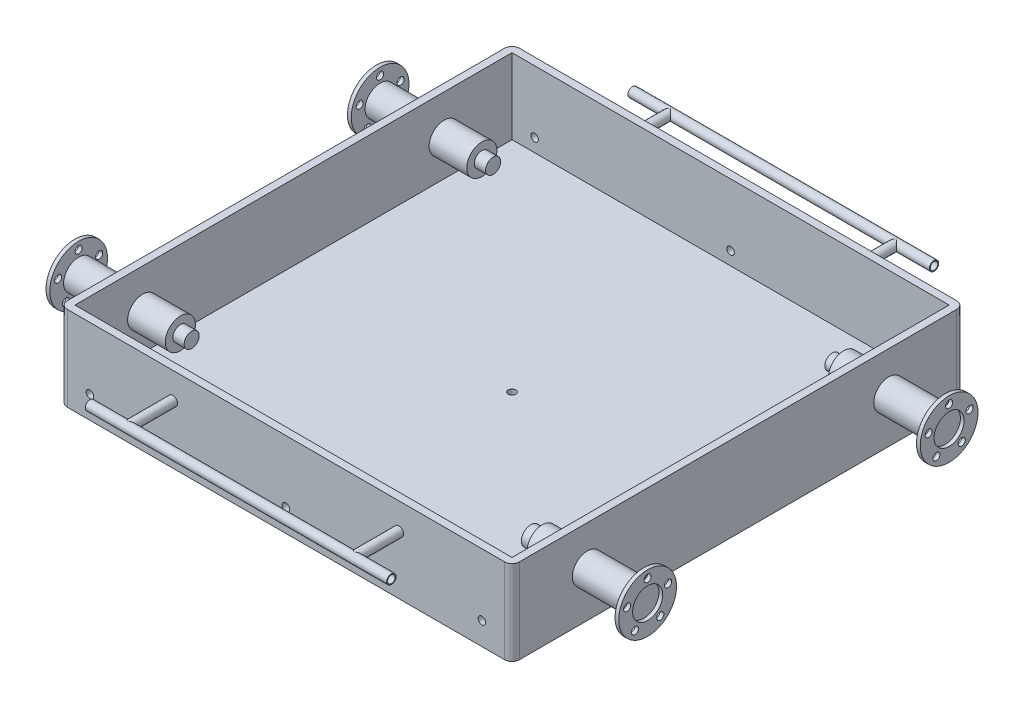
SolidWorks part; units mm, degrees
note: The reader was unsure of these and kept them because the rebuilt part matched: shared geometry of "Sketch13<3>".
ref_plane "Front Plane" through (0, 0, 0) normal (0, 0, 1) x (1, 0, 0)
ref_plane "Top Plane" through (0, 0, 0) normal (0, 1, 0) x (1, 0, 0)
ref_plane "Right Plane" through (0, 0, 0) normal (1, 0, 0) x (0, 0, -1)
sketch "Sketch1" plane through (0, 0, 0) normal (0, 1, 0) x (1, 0, 0)
  line L0 (-580, 580) -> (-580, -580)
  line L1 (-580, 600) -> (580, 600)
  line L2 (-600, 580) -> (-600, -580)
  line L3 (-580, -600) -> (580, -600)
  line L4 (600, 580) -> (600, -580)
  line L5 (-600, 600) -> (600, -600) construction
  line L6 (-600, -600) -> (600, 600) construction
  line L7 (-580, -580) -> (580, -580)
  line L8 (580, 580) -> (580, -580)
  line L9 (-580, 580) -> (580, 580)
  arc A0 (580, -600) -> (600, -580) centre (580, -580) ccw
  arc A1 (-580, 600) -> (-600, 580) centre (-580, 580) ccw
  arc A2 (-600, -580) -> (-580, -600) centre (-580, -580) ccw
  arc A3 (580, 600) -> (600, 580) centre (580, 580) cw
  arc A4 (-580, -580) -> (-580, -580) centre (-580, -580) ccw
  arc A5 (580, -580) -> (580, -580) centre (580, -580) ccw
  arc A6 (580, 580) -> (580, 580) centre (580, 580) cw
  arc A7 (-580, 580) -> (-580, 580) centre (-580, 580) ccw
  point P0 (0, 0)
  dimension "D3" = 20
  dimension "D4" = 20
  dimension "D1" = 1200
  dimension "D2" = 1200
  dimension "D5" = 20
extrude "Boss-Extrude1" add sketch "Sketch1" along normal blind 200
sketch "Sketch2" plane through (-600, 0, 0) normal (-1, 0, 0) x (0, 0, 1)
  line L1 (-600, 0) -> (600, 0)
  line L2 (-600, 0) -> (-600, -25)
  line L3 (-600, -25) -> (600, -25)
  line L4 (600, 0) -> (600, -25)
  dimension "D1" = 25
extrude "Boss-Extrude2" add sketch "Sketch2" against normal up to surface (1200 mm away) up to face at (600, 100, 0)
sketch "Sketch5" plane through (0, 0, 0) normal (0, 1, 0) x (1, 0, 0)
  line L0 (600, -580) -> (600, -600) construction
  line L1 (600, -600) -> (580, -600) construction
  line L2 (600, -580) -> (600, -600)
  line L3 (600, -600) -> (580, -600)
  arc A0 (580, -600) -> (600, -580) centre (580, -580) ccw construction
  arc A1 (580, -600) -> (600, -580) centre (580, -580) ccw
extrude "Cut-Extrude1" cut sketch "Sketch5" against normal blind 300
sketch "Sketch6" plane through (0, 0, 0) normal (0, 1, 0) x (1, 0, 0)
  line L2 (-600, -580) -> (-600, -600)
  line L3 (-600, -600) -> (-580, -600)
  line L4 (-600, -580) -> (-600, -600)
  line L5 (-600, -600) -> (-580, -600)
  arc A1 (-600, -580) -> (-580, -600) centre (-580, -580) ccw
  arc A2 (-600, -580) -> (-580, -600) centre (-580, -580) ccw
  dimension "D1" = 0
extrude "Cut-Extrude2" cut sketch "Sketch6" against normal blind 300
sketch "Sketch7" plane through (0, 0, 0) normal (0, 1, 0) x (1, 0, 0)
  line L2 (600, 580) -> (600, 600)
  line L3 (600, 600) -> (580, 600)
  line L4 (600, 580) -> (600, 600)
  line L5 (600, 600) -> (580, 600)
  arc A1 (600, 580) -> (580, 600) centre (580, 580) ccw
  arc A2 (600, 580) -> (580, 600) centre (580, 580) ccw
  dimension "D1" = 0
extrude "Cut-Extrude3" cut sketch "Sketch7" against normal blind 300
sketch "Sketch8" plane through (0, 0, 0) normal (0, 1, 0) x (1, 0, 0)
  line L2 (-580, 600) -> (-600, 600)
  line L3 (-600, 600) -> (-600, 580)
  line L4 (-580, 600) -> (-600, 600)
  line L5 (-600, 600) -> (-600, 580)
  arc A1 (-580, 600) -> (-600, 580) centre (-580, 580) ccw
  arc A2 (-580, 600) -> (-600, 580) centre (-580, 580) ccw
  dimension "D1" = 0
extrude "Cut-Extrude4" cut sketch "Sketch8" against normal blind 300
sketch "Sketch13" plane through (600, 0, 0) normal (1, 0, 0) x (0, 0, -1)
  line L0 (-600, 200) -> (-600, -25) construction
  line L1 (600, 200) -> (600, -25) construction
  line L2 (-580, -25) -> (580, -25) construction
  circle A0 centre (-400, 95) radius 40
  circle A1 centre (400, 95) radius 40
  circle A2 centre (-400, 95) radius 20
  circle A3 centre (400, 95) radius 20
  dimension "D1" = 80
  dimension "D2" = 80
  dimension "D7" = 40
  dimension "D8" = 40
  dimension "D3" = 200
  dimension "D4" = 200
  dimension "D5" = 120
  dimension "D6" = 120
extrude "Cut-Extrude8" cut sketch "Sketch13" against normal through all contours A2 | A3
extrude "Boss-Extrude7" add sketch "Sketch13<3>" along normal blind 150 and the other way blind 120
sketch "Sketch13<3>" plane through (600, 0, 0) normal (1, 0, 0) x (0, 0, -1) same geometry as "Sketch13"
sketch "Sketch14" plane through (750, 0, 0) normal (1, 0, 0) x (0, 0, -1)
  circle A0 centre (-400, 95) radius 76.655
  circle A1 centre (-400, 95) radius 40
  dimension "D1" = 153.31
extrude "Boss-Extrude8" add sketch "Sketch14" along normal blind 10 separate body
sketch "Sketch15" plane through (760, 0, 0) normal (1, 0, 0) x (0, 0, -1)
  line L0 (-400, 95) -> (-400, 234.5442) construction
  circle A0 centre (-400, 95) radius 57.15 construction
  circle A1 centre (-400, 152.15) radius 9.525
  circle A2 centre (400.6145, 1139.8014) radius 9.525
  circle A3 centre (346.2616, 1122.141) radius 57.15 construction
  circle A4 centre (1587.3303, 683.5728) radius 9.525
  circle A5 centre (1553.7384, 729.8081) radius 57.15 construction
  circle A6 centre (1520.1464, -586.0434) radius 9.525
  circle A7 centre (1553.7384, -539.8081) radius 57.15 construction
  circle A8 centre (291.9088, -914.4807) radius 9.525
  circle A9 centre (346.2616, -932.141) radius 57.15 construction
  circle A10 centre (-345.6471, 112.6603) radius 9.525
  circle A11 centre (-400, 95) radius 57.15 construction
  circle A12 centre (-366.4081, 48.7647) radius 9.525
  circle A13 centre (-400, 95) radius 57.15 construction
  circle A14 centre (-433.5919, 48.7647) radius 9.525
  circle A15 centre (-400, 95) radius 57.15 construction
  circle A16 centre (-454.3529, 112.6603) radius 9.525
  circle A17 centre (-400, 95) radius 57.15 construction
  point P25 (680, 95)
  point P38 (-400, 95)
  dimension "D1" = 114.3
  dimension "D2" = 19.05
  dimension "D3" = 5
  dimension "D4" = 5
extrude "Cut-Extrude9" cut sketch "Sketch15" against normal blind 10
sketch "Sketch18" plane through (750, 0, 0) normal (1, 0, 0) x (0, 0, -1)
  circle A0 centre (400, 95) radius 76.655
  circle A1 centre (400, 95) radius 40 construction
  circle A2 centre (400, 95) radius 40
  dimension "D1" = 153.31
extrude "Boss-Extrude9" add sketch "Sketch18" along normal blind 10 separate body
sketch "Sketch19" plane through (760, 0, 0) normal (1, 0, 0) x (0, 0, -1)
  line L0 (400, 95) -> (400, 254.3445) construction
  circle A0 centre (400, 95) radius 57.155 construction
  circle A1 centre (400, 152.155) radius 9.525
  circle A2 centre (454.3576, 112.6619) radius 9.525
  circle A3 centre (433.5949, 48.7606) radius 9.525
  circle A4 centre (366.4051, 48.7606) radius 9.525
  circle A5 centre (345.6424, 112.6619) radius 9.525
  point P17 (400, 95)
  dimension "D1" = 114.31
  dimension "D2" = 19.05
  dimension "D3" = 5
extrude "Cut-Extrude11" cut sketch "Sketch19" against normal blind 10
sketch "Sketch20" plane through (-600, 0, 0) normal (-1, 0, 0) x (0, 0, 1)
  circle A0 centre (400, 95) radius 20
  circle A1 centre (400, 95) radius 40
  circle A2 centre (-400, 95) radius 20
  circle A3 centre (-400, 95) radius 40
extrude "Boss-Extrude10" add sketch "Sketch20" along normal blind 150 and the other way blind 120
sketch "Sketch21" plane through (-750, 0, 0) normal (-1, 0, 0) x (0, 0, 1)
  circle A0 centre (-400, 95) radius 76.655
  circle A1 centre (400, 95) radius 76.655
  circle A2 centre (-400, 95) radius 57.15 construction
  circle A3 centre (400, 95) radius 57.15 construction
  circle A4 centre (-400, 152.15) radius 9.525
  circle A5 centre (-345.6471, 112.6603) radius 9.525
  circle A6 centre (-400, 95) radius 57.15 construction
  circle A7 centre (-366.4081, 48.7647) radius 9.525
  circle A8 centre (-400, 95) radius 57.15 construction
  circle A9 centre (-433.5919, 48.7647) radius 9.525
  circle A10 centre (-400, 95) radius 57.15 construction
  circle A11 centre (-454.3529, 112.6603) radius 9.525
  circle A12 centre (-400, 95) radius 57.15 construction
  circle A14 centre (400, 152.15) radius 9.525
  circle A15 centre (454.3529, 112.6603) radius 9.525
  circle A16 centre (433.5919, 48.7647) radius 9.525
  circle A17 centre (366.4081, 48.7647) radius 9.525
  circle A18 centre (345.6471, 112.6603) radius 9.525
  circle A19 centre (-400, 95) radius 40
  circle A20 centre (400, 95) radius 40
  point P25 (-400, 95)
  point P36 (400, 95)
  dimension "D1" = 114.3
  dimension "D2" = 114.3
  dimension "D3" = 153.31
  dimension "D4" = 153.31
  dimension "D6" = 19.05
  dimension "D8" = 19.05
  dimension "D5" = 5
  dimension "D7" = 5
extrude "Boss-Extrude11" add sketch "Sketch21" along normal blind 10
sketch3d "3DSketch1" plane through (0, 0, 0) normal (0, 0, 1) x (1, 0, 0)
sketch "Sketch22" plane through (-750, 0, 0) normal (-1, 0, 0) x (0, 0, 1)
  circle A0 centre (-400, 95) radius 20
extrude "Boss-Extrude12" add sketch "Sketch22" against normal blind 300
sketch "Sketch23" plane through (-750, 0, 0) normal (-1, 0, 0) x (0, 0, 1)
  circle A0 centre (400, 95) radius 20
extrude "Boss-Extrude13" add sketch "Sketch23" against normal blind 300
sketch "Sketch24" plane through (750, 0, 0) normal (1, 0, 0) x (0, 0, -1)
  circle A0 centre (-400, 95) radius 25.2634
  circle A1 centre (400, 95) radius 20
extrude "Boss-Extrude14" add sketch "Sketch24" against normal blind 300
ref_plane "Plane1" through (0, 0, -720) normal (0, 0, -1) x (-1, 0, 0)
sketch "Sketch25" plane through (0, 0, -720) normal (0, 0, -1) x (-1, 0, 0)
  line L0 (-400, 130) -> (400, 130)
  line L1 (0, 0) -> (0, 186.0042) construction
  line L2 (-580, 200) -> (580, 200) construction
  dimension "D1" = 400
  dimension "D2" = 400
  dimension "D3" = 70
other "Round end 25 X 2.4(1)" corner treatment miter
ref_plane "Plane3" through (400, 130, -720) normal (-1, 0, 0) x (0, 1, 0)
sketch "Sketch114" plane through (400, 130, -720) normal (-1, 0, 0) x (0, 1, 0)
  circle A0 centre (0, 0) radius 10.1
  circle A1 centre (0, 0) radius 12.5
  point P3 (0, 0)
  dimension "Out_dia" = 25
  dimension "D1" = 2.4
sketch "Sketch115" plane through (0, 0, -600) normal (0, 0, -1) x (-1, 0, 0)
  line L0 (-400, 130) -> (400, 130) construction
  line L1 (0, 0) -> (0, 186.0042) construction
  circle A0 centre (-300, 130) radius 12.5
  circle A1 centre (300, 130) radius 12.5
  dimension "D3" = 25
  dimension "D4" = 25
  dimension "D1" = 300
  dimension "D2" = 300
extrude "Boss-Extrude15" add sketch "Sketch115" along normal up to surface (107.5 mm away) separate body up to face at (-400, 130, -707.5)
ref_plane "Plane4" through (0, 0, 720) normal (0, 0, 1) x (1, 0, 0)
sketch "Sketch116" plane through (0, 0, 720) normal (0, 0, 1) x (1, 0, 0)
  line L0 (-400, 130) -> (400, 130)
other "Round end 25 X 2.4(2)" corner treatment miter
ref_plane "Plane5" through (-400, 130, 720) normal (1, 0, 0) x (0, 1, 0)
sketch "Sketch117" plane through (-400, 130, 720) normal (1, 0, 0) x (0, 1, 0)
  circle A0 centre (0, 0) radius 10.1
  circle A1 centre (0, 0) radius 12.5
  point P3 (0, 0)
  dimension "Out_dia" = 25
  dimension "D1" = 2.4
sketch "Sketch118" plane through (0, 0, 600) normal (0, 0, 1) x (1, 0, 0)
  circle A0 centre (-300, 130) radius 12.5
  circle A1 centre (300, 130) radius 12.5
extrude "Boss-Extrude16" add sketch "Sketch118" along normal up to surface (107.5 mm away) separate body up to face at (400, 130, 707.5)
sketch "Sketch119" plane through (0, 0, 600) normal (0, 0, 1) x (1, 0, 0)
  line L1 (580, -25) -> (-580, -25) construction
  line L2 (-580, 200) -> (-580, -25) construction
  line L3 (580, 200) -> (580, -25) construction
  circle A0 centre (0, 35) radius 10
  circle A1 centre (-520, 35) radius 10
  circle A2 centre (520, 35) radius 10
  point P7 (0, 0)
  point P8 (0, 0)
  dimension "D1" = 20
  dimension "D2" = 20
  dimension "D3" = 20
  dimension "D4" = 60
  dimension "D5" = 60
  dimension "D6" = 60
extrude "Cut-Extrude12" cut sketch "Sketch119" against normal blind 1242
sketch "Sketch120" plane through (0, -25, 0) normal (0, -1, 0) x (1, 0, 0)
  circle A0 centre (0, 0) radius 10
  dimension "D1" = 20
extrude "Cut-Extrude13" cut sketch "Sketch120" against normal blind 25
